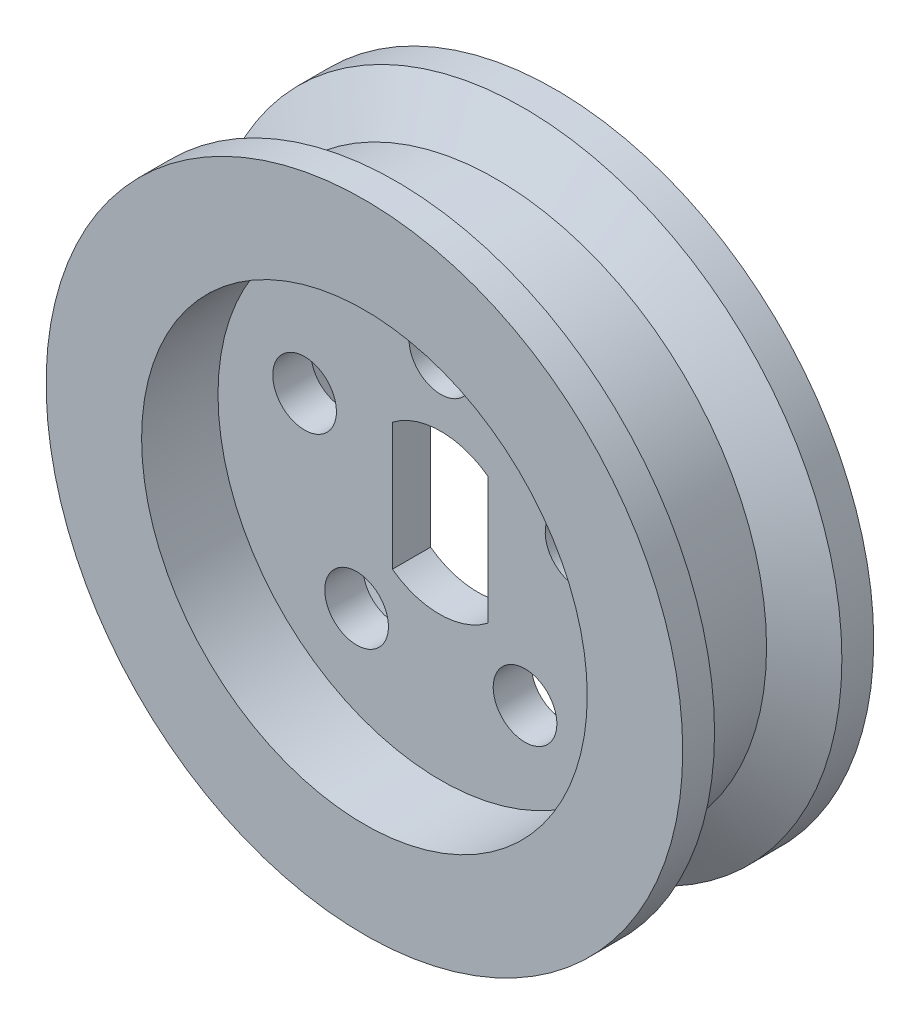
SolidWorks part; units mm, degrees
ref_plane "Front Plane" through (0, 0, 0) normal (0, 0, 1) x (1, 0, 0)
ref_plane "Top Plane" through (0, 0, 0) normal (0, 1, 0) x (1, 0, 0)
ref_plane "Right Plane" through (0, 0, 0) normal (1, 0, 0) x (0, 0, -1)
sketch "Sketch1" plane through (0, 0, 0) normal (0, 0, 1) x (1, 0, 0)
  line L0 (-1.5216, 1.9836) -> (-1.5216, -2.0164)
  line L1 (1.4783, 2.0161) -> (1.4783, -1.9839)
  circle A0 centre (0, 0) radius 10
  arc A2 (-1.5216, 1.9836) -> (1.4783, 2.0161) centre (0, 0) cw
  arc A3 (-1.5216, -2.0164) -> (1.4783, -1.9839) centre (-0.0433, -0.0002) ccw
extrude "Boss-Extrude1" add sketch "Sketch1" along normal mid plane 6
sketch "Sketch2" plane through (0, 0, 3) normal (0, 0, 1) x (1, 0, 0)
  circle A0 centre (0, 0) radius 7
  dimension "D1" = 14
extrude "Cut-Extrude1" cut sketch "Sketch2" against normal blind 2.4
sketch "Sketch3" plane through (0, 0, 0.6) normal (0, 0, 1) x (1, 0, 0)
  circle A0 centre (0, 4.5) radius 1
  dimension "D1" = 4.5
extrude "Cut-Extrude2" cut sketch "Sketch3" against normal through all
pattern_circular "CirPattern1" count 5 over 360 about axis through (0, 0, 3) along (0, 0, -1) of "Cut-Extrude2"
ref_plane "Plane1" through (-1.5216, -2.0164, 0.6) normal (0.8065, -0.5913, 0) x (0, 0, -1)
mirror "Mirror1" about plane through (0, 0, 0) normal (0, 0, 1) of "Cut-Extrude1"
sketch "Sketch5" plane through (0, 0, 0) normal (0, 1, 0) x (1, 0, 0)
  line L0 (0, 0) -> (0, 5.2467) construction
  line L1 (-10, 2) -> (-8.5, 1.134)
  line L2 (-10, 3) -> (-10, -3) construction
  line L3 (-8.5, 1.134) -> (-8.5, -1.134)
  line L4 (-8.5, -1.134) -> (-10, -2)
  line L5 (-10, -2) -> (-10, 2)
  point P8 (0, 0)
  point P10 (-10, 0)
  dimension "D1" = 1
  dimension "D2" = 1
  dimension "D3" = 60
  dimension "D4" = 60
  dimension "D5" = 1.5
revolve "Cut-Revolve1" cut sketch "Sketch5" angle 360 about L0
